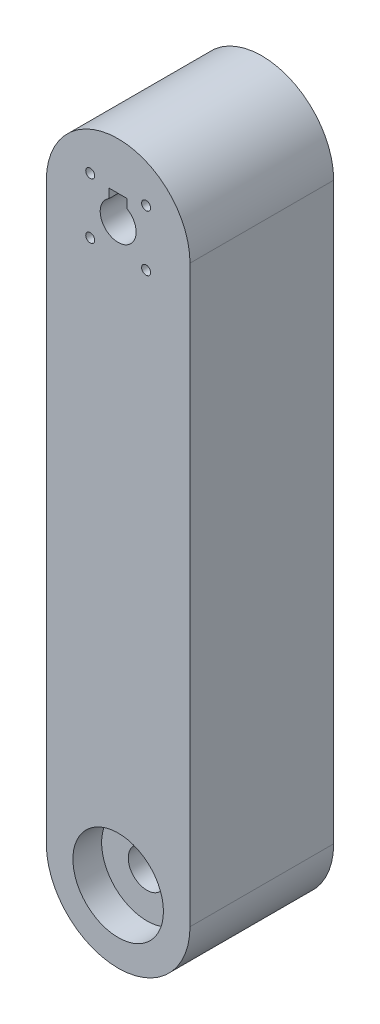
SolidWorks part; units mm, degrees
ref_plane "Front Plane" through (0, 0, 0) normal (0, 0, 1) x (1, 0, 0)
ref_plane "Top Plane" through (0, 0, 0) normal (0, 1, 0) x (1, 0, 0)
ref_plane "Right Plane" through (0, 0, 0) normal (1, 0, 0) x (0, 0, -1)
sketch "Sketch1" plane through (0, 0, 0) normal (0, 0, 1) x (1, 0, 0)
  line L2 (12.7, 50.8) -> (12.7, -50.8)
  line L4 (-12.7, 50.8) -> (-12.7, -50.8)
  line L5 (12.7, 50.8) -> (-12.7, -50.8) construction
  line L6 (12.7, -50.8) -> (-12.7, 50.8) construction
  arc A0 (-12.7, 50.8) -> (12.7, 50.8) centre (0, 50.8) cw
  arc A1 (-12.7, -50.8) -> (12.7, -50.8) centre (0, -50.8) ccw
  point P0 (0, 0)
  dimension "D1" = 101.6
  dimension "D2" = 25.4
extrude "Boss-Extrude1" add sketch "Sketch1" along normal blind 25.4
sketch "Sketch2" plane through (0, 0, 25.4) normal (0, 0, 1) x (1, 0, 0)
  line L0 (-4.9391, 55.7391) -> (4.9391, 45.8609) construction
  line L1 (4.9391, 55.7391) -> (-4.9391, 45.8609) construction
  line L2 (0, 50.8) -> (0, 59.0413) construction
  circle A0 centre (0, 50.8) radius 3.175
  circle A1 centre (-4.9391, 55.7391) radius 0.7938
  circle A2 centre (-4.9391, 45.8609) radius 0.7937
  circle A3 centre (4.9391, 55.7391) radius 0.7938
  circle A4 centre (4.9391, 45.8609) radius 0.7938
  point P8 (0, 50.8)
  point P9 (0, 50.8)
  dimension "D1" = 6.35
  dimension "D4" = 1.5875
  dimension "D2" = 45
  dimension "D3" = 13.97
extrude "Cut-Extrude1" cut sketch "Sketch2" against normal up to next
sketch "Sketch3" plane through (0, 0, 25.4) normal (0, 0, 1) x (1, 0, 0)
  line L1 (-1.5875, 55.1371) -> (1.5875, 55.1371)
  line L2 (-1.5875, 55.1371) -> (-1.5875, 53.5496)
  line L3 (-1.5875, 53.5496) -> (1.5875, 53.5496)
  line L4 (1.5875, 55.1371) -> (1.5875, 53.5496)
  circle A0 centre (0, 50.8) radius 3.175 construction
  dimension "D1" = 3.175
  dimension "D2" = 1.5875
extrude "Cut-Extrude2" cut sketch "Sketch3" against normal through all
sketch "Sketch4" plane through (0, 0, 25.4) normal (0, 0, 1) x (1, 0, 0)
  circle A0 centre (0, -50.8) radius 8.001
  point P2 (0, 0)
  point P5 (0, 0)
  dimension "D1" = 16.002
extrude "Cut-Extrude3" cut sketch "Sketch4" against normal blind 5.08
ref_plane "Plane1" through (0, 0, 12.7) normal (0, 0, 1) x (1, 0, 0)
mirror "Mirror1" about plane through (0, 0, 12.7) normal (0, 0, 1) of "Cut-Extrude3"
sketch "Sketch5" plane through (0, 0, 20.32) normal (0, 0, 1) x (1, 0, 0)
  circle A0 centre (0, -50.8) radius 3.302
  circle A1 centre (0, -50.8) radius 8.001 construction
  dimension "D1" = 6.604
extrude "Cut-Extrude4" cut sketch "Sketch5" against normal through all
